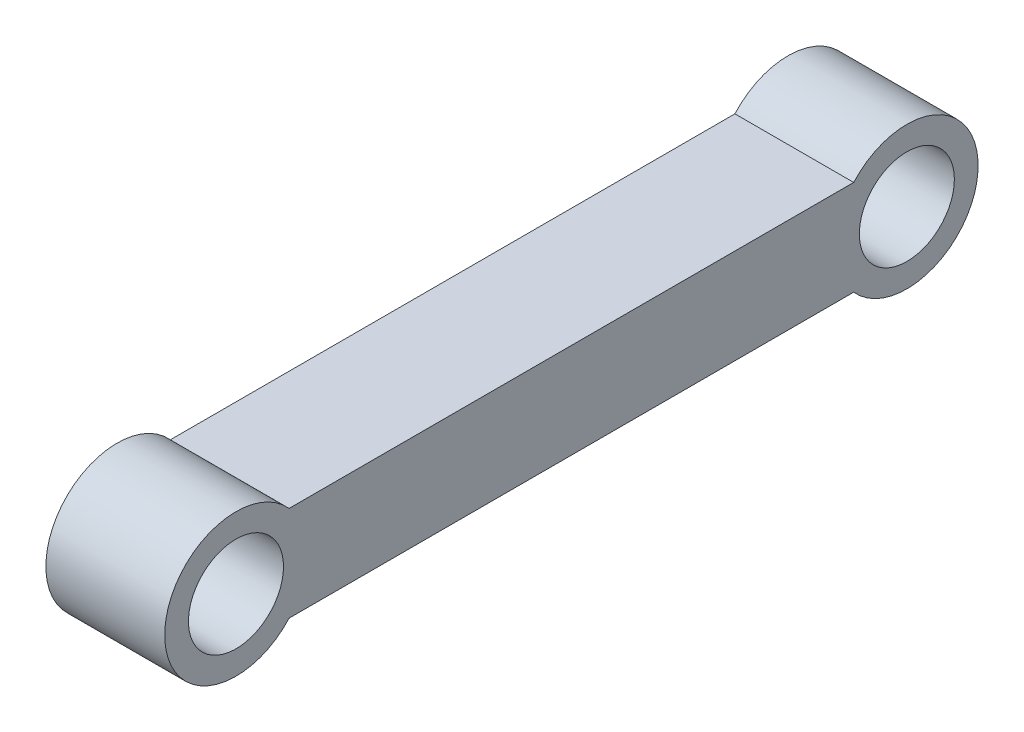
SolidWorks part; units mm, degrees
material "Thornel Mat VMA"
ref_plane "Front Plane" through (0, 0, 0) normal (0, 0, 1) x (1, 0, 0)
ref_plane "Top Plane" through (0, 0, 0) normal (0, 1, 0) x (1, 0, 0)
ref_plane "Right Plane" through (0, 0, 0) normal (1, 0, 0) x (0, 0, -1)
sketch "LinkFrame" plane through (0, 0, 0) normal (1, 0, 0) x (0, 0, -1)
  line L0 (-304.9655, -226.2633) -> (259.6545, -226.2633) construction
  line L1 (-260.2442, -186.2633) -> (214.9331, -186.2633)
  line L2 (-260.2442, -266.2633) -> (214.9331, -266.2633)
  arc A1 (214.9331, -266.2633) -> (214.9331, -186.2633) centre (259.6545, -226.2633) ccw
  arc A2 (-260.2442, -186.2633) -> (-260.2442, -266.2633) centre (-304.9655, -226.2633) ccw
  circle A5 centre (-304.9655, -226.2633) radius 40
  circle A6 centre (259.6545, -226.2633) radius 40
  dimension "D1" = 120
  dimension "D2" = 120
  dimension "D5" = 80
  dimension "D6" = 80
  dimension "D3" = 564.62
  dimension "D4" = 80
  dimension "D7" = 44.7214
  dimension "D8" = 44.7214
extrude "Boss-Extrude1" add sketch "LinkFrame" along normal blind 100
equation "\"D1@LinkFrame\" = 1.5 * \"HoleMountDiameter@PrintingPress.Assembly\""
equation "\"D2@LinkFrame\" = 1.5 * \"HoleMountDiameter@PrintingPress.Assembly\""
equation "\"LinkLength\" = 54cm + 2.462cm"
equation "\"D3@LinkFrame\" = \"LinkLength\""
equation "\"D4@LinkFrame\" = \"HoleMountDiameter@PrintingPress.Assembly\""
equation "\"D5@LinkFrame\"=\"HoleMountDiameter@PrintingPress.Assembly\""
equation "\"D6@LinkFrame\"=\"HoleMountDiameter@PrintingPress.Assembly\""
equation "\"D1@Boss-Extrude1\"=\"RivetLength@PrintingPress.Assembly\""
